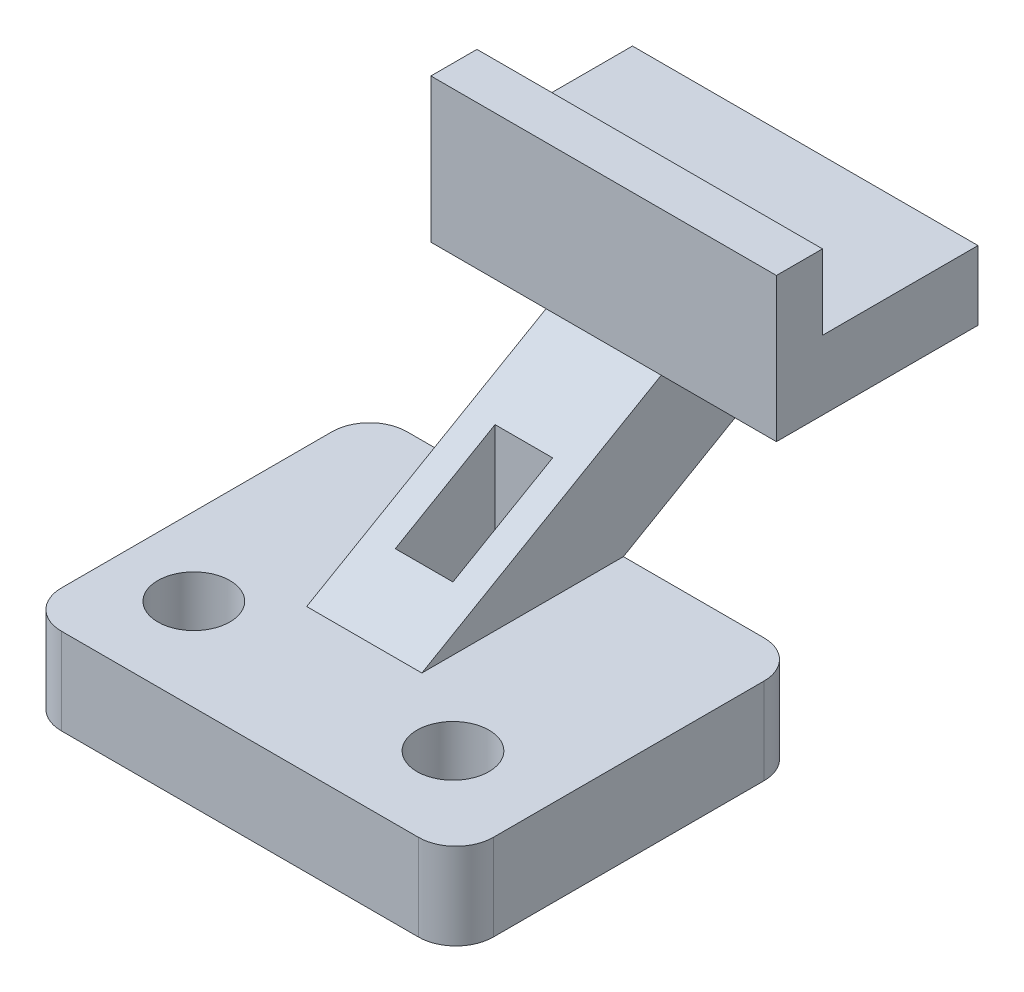
SolidWorks part; units mm, degrees
ref_plane "Front Plane" through (0, 0, 0) normal (0, 0, 1) x (1, 0, 0)
ref_plane "Top Plane" through (0, 0, 0) normal (0, 1, 0) x (1, 0, 0)
ref_plane "Right Plane" through (0, 0, 0) normal (1, 0, 0) x (0, 0, -1)
sketch "Sketch3" plane through (0, 0, 0) normal (0, 1, 0) x (1, 0, 0)
  line L0 (0, 56.8588) -> (0, -61.885) construction
  line L1 (-29.4954, 31.4019) -> (32.5046, 31.4019)
  line L2 (-35.9954, 24.9019) -> (-35.9954, -22.0981)
  line L3 (-29.4954, -28.5981) -> (32.5046, -28.5981)
  line L4 (39.0046, 24.9019) -> (39.0046, -22.0981)
  arc A0 (32.5046, 31.4019) -> (39.0046, 24.9019) centre (32.5046, 24.9019) cw
  arc A1 (39.0046, -22.0981) -> (32.5046, -28.5981) centre (32.5046, -22.0981) cw
  arc A2 (-29.4954, -28.5981) -> (-35.9954, -22.0981) centre (-29.4954, -22.0981) cw
  arc A3 (-35.9954, 24.9019) -> (-29.4954, 31.4019) centre (-29.4954, 24.9019) cw
  point P6 (39.0046, 31.4019)
  point P11 (-35.9954, -28.5981)
  point P14 (-35.9954, 31.4019)
  point P20 (0, -2.5131)
  dimension "D3" = 6.5
  dimension "D1" = 75
  dimension "D2" = 60
extrude "Boss-Extrude1" add sketch "Sketch3" along normal blind 15 contours L2 A2 L3 A1 L4 A0 L1 A3
sketch "Sketch5" plane through (0, 15, 0) normal (0, 1, 0) x (1, 0, 0)
  line L0 (-29.4954, -28.5981) -> (32.5046, -28.5981) construction
  line L1 (-22.5, -12.5981) -> (22.5, -12.5981) construction
  line L2 (0, -33.6324) -> (0, 33.6324) construction
  circle A0 centre (-22.5, -12.5981) radius 6.25
  circle A1 centre (22.5, -12.5981) radius 6.25
  point P6 (0, 0)
  point P7 (0, -12.5981)
  point P12 (0, 0)
  dimension "D1" = 16
  dimension "D2" = 45
extrude "Cut-Extrude1" cut sketch "Sketch5" against normal blind 22 contours A0 | A1
sketch "Sketch7" plane through (0, 15, 0) normal (0, 1, 0) x (1, 0, 0)
  line L0 (-29.4954, 31.4019) -> (32.5046, 31.4019) construction
  line L1 (-11.9096, -3.5981) -> (8.0904, -3.5981)
  line L2 (-11.9096, -3.5981) -> (-11.9096, 31.4019)
  line L3 (-11.9096, 31.4019) -> (8.0904, 31.4019)
  line L4 (8.0904, -3.5981) -> (8.0904, 31.4019)
  point P10 (0, 0)
  dimension "D1" = 35
  dimension "D2" = 20
sketch "Sketch15" plane through (0, 0, 0) normal (1, 0, 0) x (0, 0, -1)
  line L0 (0, 0) -> (67.55, 39) construction
  line L1 (30.9456, 15) -> (30.9456, 39) construction
  line L3 (24.9019, 15) -> (-22.0981, 15) construction
  point P3 (0, 0)
  point P8 (0, 0)
  point P9 (0, 0)
  point P10 (0, 0)
  point P11 (0, 0)
  point P12 (0, 0)
  point P13 (0, 0)
  point P14 (0, 0)
  point P15 (0, 0)
  point P16 (0, 0)
  point P17 (0, 0)
ref_axis "Axis6" through (0, 0, 0) along (0, 0.5, -0.866)
extrude "Boss-Extrude4" add sketch "Sketch7" along direction (0, 0.5, -0.866) on the side of the normal up to vertex (24 mm away) up to point (0, 39, -67.55)
sketch "Sketch19" plane through (0, 12.808, 7.3947) normal (0, 0.866, 0.5) x (1, 0, 0)
  line L0 (-1.9096, 4.384) -> (-1.9096, 52.384) construction
  line L1 (-11.9096, 4.384) -> (8.0904, 4.384) construction
  line L2 (-11.9096, 52.384) -> (8.0904, 52.384) construction
  line L4 (-6.9096, 16.384) -> (3.0904, 16.384)
  line L5 (-6.9096, 16.384) -> (-6.9096, 36.384)
  line L6 (-6.9096, 36.384) -> (3.0904, 36.384)
  line L7 (3.0904, 16.384) -> (3.0904, 36.384)
  line L8 (-6.9096, 16.384) -> (3.0904, 36.384) construction
  line L9 (-6.9096, 36.384) -> (3.0904, 16.384) construction
  point P6 (-1.9096, 26.384)
  dimension "D1" = 20
  dimension "D2" = 12
  dimension "D3" = 10
extrude "Cut-Extrude2" cut sketch "Sketch19" along direction (0, -1, 0) on the side against the normal blind 65
sketch "Sketch22" plane through (0, 39, 0) normal (0, 1, 0) x (1, 0, 0)
  line L0 (-1.9096, 72.9712) -> (-1.9096, 37.9712) construction
  line L1 (8.0904, 72.9712) -> (-11.9096, 72.9712) construction
  line L2 (-11.9096, 37.9712) -> (8.0904, 37.9712) construction
  line L3 (-11.9096, 55.4712) -> (8.0904, 55.4712) construction
  line L4 (-11.9096, 72.9712) -> (-11.9096, 37.9712) construction
  line L5 (8.0904, 37.9712) -> (8.0904, 72.9712) construction
  line L7 (-31.9096, 37.9712) -> (28.0904, 37.9712)
  line L8 (-31.9096, 37.9712) -> (-31.9096, 72.9712)
  line L9 (-31.9096, 72.9712) -> (28.0904, 72.9712)
  line L10 (28.0904, 37.9712) -> (28.0904, 72.9712)
  line L11 (-31.9096, 37.9712) -> (28.0904, 72.9712) construction
  line L12 (-31.9096, 72.9712) -> (28.0904, 37.9712) construction
  point P12 (-1.9096, 55.4712)
extrude "Boss-Extrude5" add sketch "Sketch22" along normal blind 12
sketch "Sketch23" plane through (0, 51, 0) normal (0, 1, 0) x (1, 0, 0)
  line L0 (-31.9096, 45.9712) -> (28.0904, 45.9712)
  line L1 (-31.9096, 72.9712) -> (-31.9096, 37.9712) construction
  line L2 (28.0904, 37.9712) -> (28.0904, 72.9712) construction
  line L3 (-31.9096, 37.9712) -> (28.0904, 37.9712) construction
  line L4 (-31.9096, 45.9712) -> (-31.9096, 37.9712)
  line L5 (-31.9096, 37.9712) -> (28.0904, 37.9712)
  line L6 (28.0904, 37.9712) -> (28.0904, 45.9712)
  dimension "D1" = 8
extrude "Boss-Extrude6" add sketch "Sketch23" along normal blind 13
sketch "Sketch25" plane through (0, 39, 0) normal (0, -1, 0) x (1, 0, 0)
  point P3 (-12.149, -42.0368)
ref_axis "Axis8" through (0, 15, -30.9456) along (0, 1, 0)
